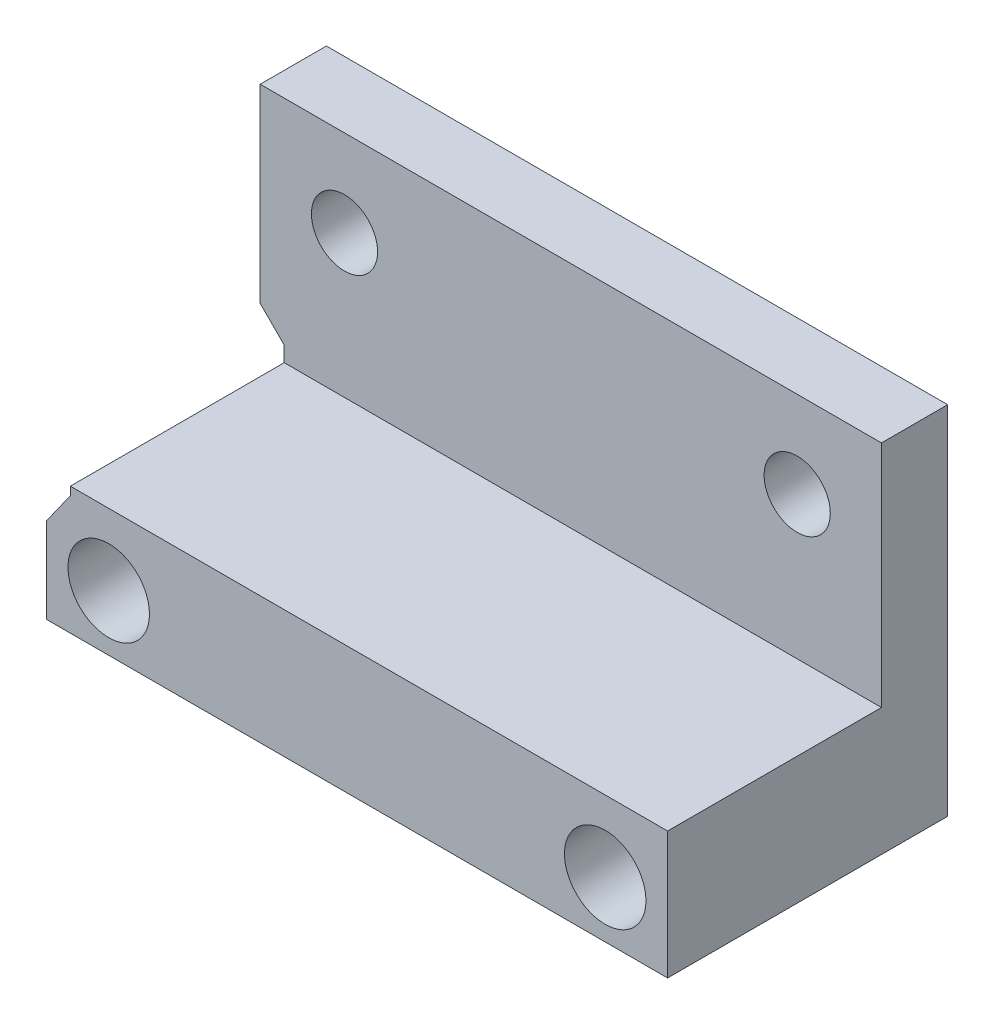
SolidWorks part; units mm, degrees
ref_plane "Front Plane" through (0, 0, 0) normal (0, 0, 1) x (1, 0, 0)
ref_plane "Top Plane" through (0, 0, 0) normal (0, 1, 0) x (1, 0, 0)
ref_plane "Right Plane" through (0, 0, 0) normal (1, 0, 0) x (0, 0, -1)
sketch "Sketch1" plane through (0, 0, 0) normal (0, 0, 1) x (1, 0, 0)
  line L1 (-12.2, 0) -> (12.2, 0)
  line L2 (-12.2, 0) -> (-12.2, 14)
  line L3 (-12.2, 14) -> (12.2, 14)
  line L4 (12.2, 0) -> (12.2, 14)
  circle A0 centre (-8.89, 10.6) radius 1.3
  circle A1 centre (8.89, 10.6) radius 1.3
  point P9 (0, 0)
  dimension "D3" = 2.6
  dimension "D1" = 14
  dimension "D2" = 24.4
  dimension "D4" = 8.89
  dimension "D5" = 8.89
  dimension "D6" = 10.6
  dimension "D7" = 17.78
extrude "Boss-Extrude1" add sketch "Sketch1" along normal blind 2.6
sketch "Sketch2" plane through (0, 0, 0) normal (0, 0, 1) x (1, 0, 0)
  line L0 (12.2, 0) -> (12.2, 14) construction
  line L1 (12.2, 5) -> (-12.2, 5)
  line L2 (12.2, 5) -> (12.2, 0)
  line L3 (12.2, 0) -> (-12.2, 0)
  line L4 (-12.2, 5) -> (-12.2, 0)
  dimension "D1" = 5
extrude "Boss-Extrude2" add sketch "Sketch2" along normal blind 11
sketch "Sketch3" plane through (0, 0, 11) normal (0, 0, 1) x (1, 0, 0)
  circle A0 centre (-9.75, 2.2) radius 1.6
  circle A1 centre (9.75, 2.2) radius 1.6
  dimension "D3" = 3.2
  dimension "D1" = 9.75
  dimension "D2" = 9.75
  dimension "D4" = 2.2
extrude "Cut-Extrude1" cut sketch "Sketch3" against normal blind 4.6
sketch "Sketch4" plane through (0, 0, 11) normal (0, 0, 1) x (1, 0, 0)
  line L0 (-12.2, 3.3436) -> (-11.257, 4.6756)
  line L1 (-12.2, 5) -> (-12.2, 0) construction
  line L2 (-11.257, 4.6756) -> (-11.257, 5.6006)
  line L3 (-11.257, 5.6006) -> (-12.2, 6.5436)
  line L4 (-12.2, 14) -> (-12.2, 5) construction
  line L5 (-12.2, 6.5436) -> (-12.2, 3.3436)
extrude "Cut-Extrude2" cut sketch "Sketch4" against normal through all
equation "\"D4@Sketch1\"=2.54*7/2"
